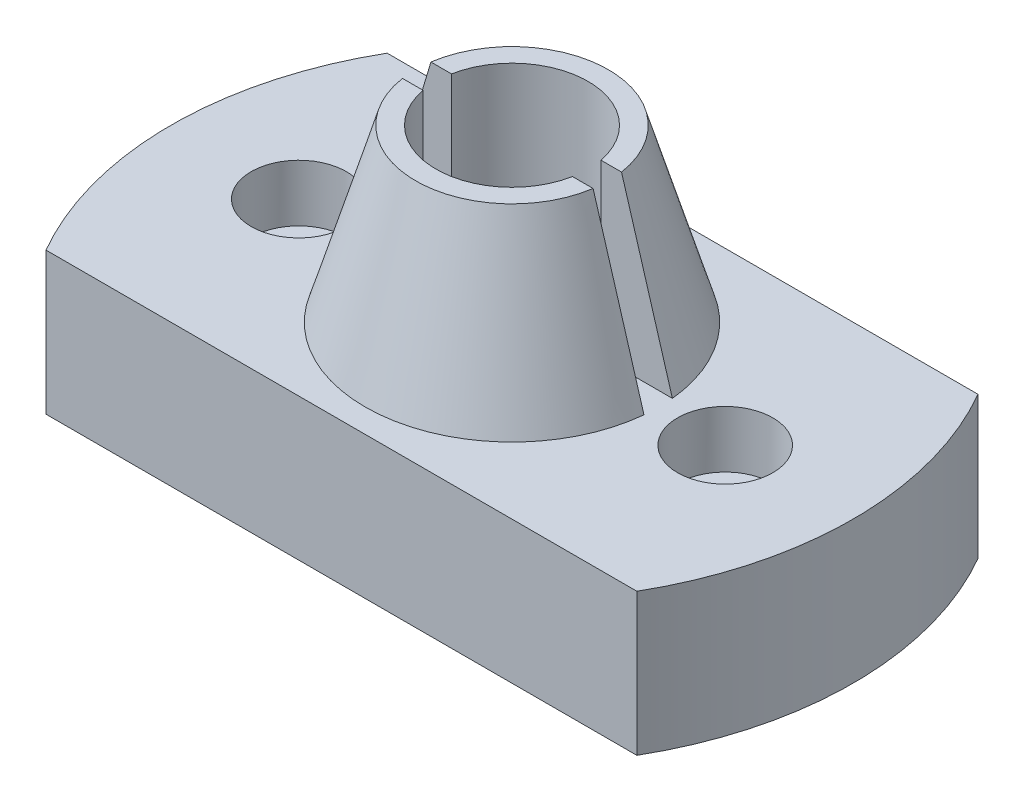
SolidWorks part; units mm, degrees
ref_plane "Front Plane" through (0, 0, 0) normal (0, 0, 1) x (1, 0, 0)
ref_plane "Top Plane" through (0, 0, 0) normal (0, 1, 0) x (1, 0, 0)
ref_plane "Right Plane" through (0, 0, 0) normal (1, 0, 0) x (0, 0, -1)
sketch "Sketch1" plane through (0, 0, 0) normal (0, 1, 0) x (1, 0, 0)
  circle A0 centre (0, 0) radius 12
  circle A1 centre (0, 0) radius 2.675
  dimension "D1" = 24
  dimension "D2" = 5.35
extrude "Boss-Extrude1" add sketch "Sketch1" along normal blind 5
sketch "Sketch2" plane through (0, 5, 0) normal (0, 1, 0) x (1, 0, 0)
  circle A0 centre (0, 0) radius 5.1666
  circle A1 centre (0, 0) radius 2.675
  dimension "D1" = 10.3333
extrude "Boss-Extrude2" add sketch "Sketch2" along normal blind 6
chamfer "Chamfer1" distance 6 angle 16.5 1 edges at (0, 11, 5.1666) first distance on face at (0, 11, 5.1666)
sketch "Sketch3" plane through (0, 5, 0) normal (0, 1, 0) x (1, 0, 0)
  line L0 (-7.5, 0) -> (7.5, 0) construction
  circle A2 centre (-7.5, 0) radius 1.675
  circle A3 centre (7.5, 0) radius 1.675
  dimension "D1" = 3.35
  dimension "D2" = 15
extrude "Cut-Extrude1" cut sketch "Sketch3" against normal blind 6
sketch "Sketch4" plane through (0, 0, 0) normal (0, -1, 0) x (1, 0, 0)
  line L0 (0, 0) -> (0, 12) construction
  line L1 (-10.425, -1.6887) -> (-7.5, -3.3775)
  line L2 (-7.5, -3.3775) -> (-4.575, -1.6887)
  line L3 (-4.575, -1.6887) -> (-4.575, 1.6887)
  line L4 (-4.575, 1.6887) -> (-7.5, 3.3775)
  line L5 (-7.5, 3.3775) -> (-10.425, 1.6887)
  line L6 (-10.425, 1.6887) -> (-10.425, -1.6887)
  line L7 (10.425, 1.6887) -> (10.425, -1.6887)
  line L8 (7.5, 3.3775) -> (10.425, 1.6887)
  line L9 (4.575, 1.6887) -> (7.5, 3.3775)
  line L10 (4.575, -1.6887) -> (4.575, 1.6887)
  line L11 (7.5, -3.3775) -> (4.575, -1.6887)
  line L12 (10.425, -1.6887) -> (7.5, -3.3775)
  circle A0 centre (-7.5, 0) radius 2.925 construction
  circle A1 centre (0, 0) radius 12 construction
  circle A2 centre (7.5, 0) radius 2.925 construction
  dimension "D1" = 5.85
extrude "Cut-Extrude2" cut sketch "Sketch4" against normal blind 2.5
sketch "Sketch5" plane through (0, 5, 0) normal (0, 1, 0) x (1, 0, 0)
  line L0 (-5.1666, 0) -> (5.1666, 0) construction
  line L1 (-5.1666, -0.5) -> (5.1666, -0.5)
  line L2 (-5.1666, 0.5) -> (5.1666, 0.5)
  line L3 (-5.1666, 0.5) -> (-5.1666, -0.5)
  line L4 (5.1666, 0.5) -> (5.1666, -0.5)
  circle A0 centre (0, 0) radius 5.1666 construction
  dimension "D1" = 0.5
  dimension "D2" = 0.5
extrude "Cut-Extrude3" cut sketch "Sketch5" along normal blind 6
sketch "Sketch6" plane through (0, 0, 0) normal (0, -1, 0) x (1, 0, 0)
  line L0 (-12, 0) -> (12, 0) construction
  line L1 (-10.3923, 6) -> (10.3923, 6)
  line L2 (-10.3923, -6) -> (10.3923, -6)
  line L4 (-12, 6) -> (12, 6) construction
  line L5 (-12, -6) -> (12, -6) construction
  circle A0 centre (0, 0) radius 12 construction
  arc A1 (-10.3923, -6) -> (10.3923, -6) centre (0, 0) ccw
  arc A2 (10.3923, 6) -> (-10.3923, 6) centre (0, 0) ccw
  dimension "D1" = 6
  dimension "D2" = 6
extrude "Cut-Extrude4" cut sketch "Sketch6" against normal blind 10
sketch "Sketch7" plane through (0, 2.5, 0) normal (0, -1, 0) x (1, 0, 0)
  circle A0 centre (7.5, 0) radius 1.7061
  circle A1 centre (-7.5, 0) radius 1.675
extrude "Boss-Extrude3" add sketch "Sketch7" against normal blind 0.5
